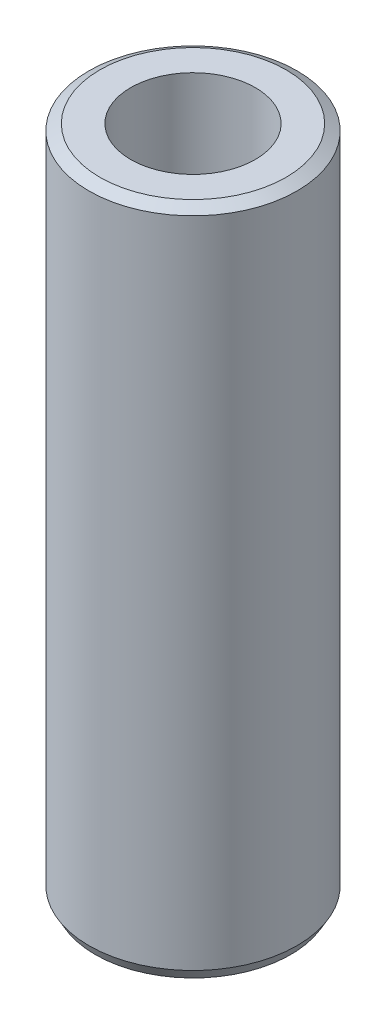
SolidWorks part; units mm, degrees
ref_plane "Front Plane" through (0, 0, 0) normal (0, 0, 1) x (1, 0, 0)
ref_plane "Top Plane" through (0, 0, 0) normal (0, 1, 0) x (1, 0, 0)
ref_plane "Right Plane" through (0, 0, 0) normal (1, 0, 0) x (0, 0, -1)
sketch "Sketch1" plane through (0, 0, 0) normal (0, 1, 0) x (1, 0, 0)
  circle A0 centre (0, 0) radius 7.5
  dimension "SHAFT_OD" = 15
extrude "Boss-Extrude1" add sketch "Sketch1" along normal blind 48.341
sketch "Sketch2" plane through (0, 0, 0) normal (0, 1, 0) x (1, 0, 0)
  circle A0 centre (0, 0) radius 4.4916
  dimension "BORE_D" = 8.9833
extrude "Cut-Extrude1" cut sketch "Sketch2" along normal through all
chamfer "Chamfer1" distance 0.456 angle 60 2 edges at (0, 48.341, 7.5) (0, 0, 7.5) first distance on face at (0, 48.341, 7.5) first distance on face at (0, 0, 4.4916)
